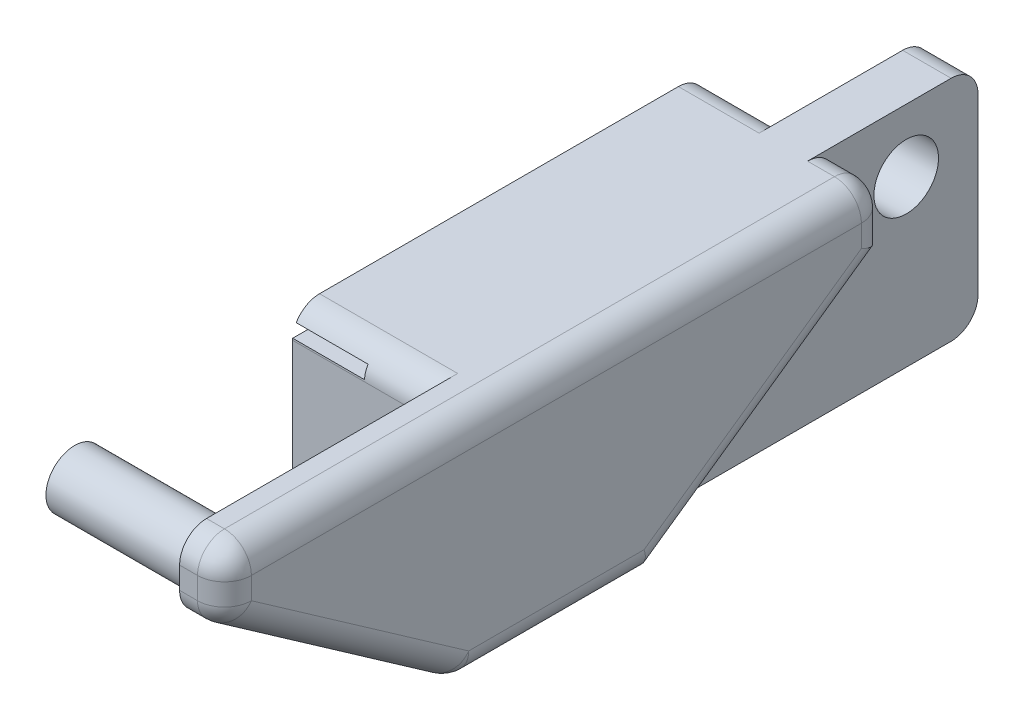
SolidWorks part; units mm, degrees
ref_plane "Front Plane" through (0, 0, 0) normal (0, 0, 1) x (1, 0, 0)
ref_plane "Top Plane" through (0, 0, 0) normal (0, 1, 0) x (1, 0, 0)
ref_plane "Right Plane" through (0, 0, 0) normal (1, 0, 0) x (0, 0, -1)
sketch "Sketch1" plane through (0, 0, 0) normal (0, 1, 0) x (1, 0, 0)
  line L0 (-28.7782, 18.5442) -> (-24.2782, 18.5442)
  line L1 (-24.2782, 18.5442) -> (-24.2782, 26.5442)
  line L2 (-24.2782, 26.5442) -> (-21.5782, 26.5442)
  line L3 (-21.5782, 26.5442) -> (-21.5782, 18.5442)
  line L4 (-21.5782, 18.5442) -> (-18.5782, 18.5442)
  line L5 (-18.5782, 18.5442) -> (-18.5782, -18.4558)
  line L6 (-18.5782, -18.4558) -> (-21.0782, -18.4558)
  line L7 (-21.0782, -18.4558) -> (-21.0782, -4.4558)
  line L10 (-21.0782, -4.4558) -> (-28.7782, -4.4558)
  line L11 (-28.7782, -4.4558) -> (-28.7782, 18.5442)
  dimension "D1" = 10.2
  dimension "D2" = 3
  dimension "D3" = 4.5
  dimension "D4" = 8
  dimension "D5" = 14
  dimension "D6" = 7.7
  dimension "D7" = 45
  dimension "D8" = 8
extrude "Boss-Extrude1" add sketch "Sketch1" along normal blind 12.7
sketch "Sketch2" plane through (-28.7782, 0, 0) normal (-1, 0, 0) x (0, 0, 1)
  line L0 (-26.5442, 12.7) -> (-26.5442, 0)
  line L1 (-26.5442, 0) -> (15.1247, 0)
  line L2 (15.1247, 0) -> (18.4558, 9.2)
  line L3 (18.4558, 9.2) -> (18.4558, 12.7)
  line L4 (18.4558, 12.7) -> (-26.5442, 12.7)
  line L5 (-26.5442, 9.2) -> (18.4558, 9.2) construction
  line L6 (-22.5442, 12.7) -> (-22.5442, 0) construction
  line L7 (-15.2942, 12.7) -> (-15.2942, 0) construction
  line L8 (15.2058, 12.7) -> (15.2058, 0.224) construction
  line L9 (-18.5442, 5.7649) -> (-7.0404, 0)
  line L11 (4.4558, 0) -> (4.4558, 12.7)
  line L13 (-18.5442, 12.7) -> (-18.5442, 5.7649)
  line L14 (-18.5442, 12.7) -> (4.4558, 12.7)
  line L15 (15.1247, 0) -> (18.4558, 0)
  line L16 (-18.5442, 0) -> (4.4558, 0) construction
  line L17 (-18.5442, 12.7) -> (4.4558, 12.7) construction
  line L18 (-7.0404, 0) -> (4.4558, 0)
  line L19 (-18.5442, 5.7649) -> (-18.5442, 0)
  line L20 (-18.5442, 0) -> (-7.0404, 0)
  line L21 (18.4558, 0) -> (18.4558, 9.2)
  line L22 (15.2058, 10.8) -> (-26.5442, 10.8) construction
  line L23 (-26.5442, 11.3) -> (18.4558, 11.3) construction
  line L24 (-18.5442, 12.7) -> (-18.5442, 0) construction
  line L25 (18.4558, 11.95) -> (-26.5442, 11.95)
  line L26 (18.4558, 11.95) -> (18.4558, 11.3)
  line L27 (18.4558, 11.3) -> (-26.5442, 11.3)
  line L28 (-26.5442, 11.95) -> (-26.5442, 11.3)
  line L29 (-18.5442, 12.7) -> (-18.5442, 0) construction
  circle A3 centre (15.2058, 9.2) radius 1.6
  circle A4 centre (-15.2942, 9.2) radius 1.6
  circle A5 centre (-22.5442, 9.2) radius 1.8
  point P35 (-18.5442, 0)
  line M18 (-18.5442, 0) -> (4.4558, 0)
  line M21 (-18.5442, 12.7) -> (-18.5442, 0)
  dimension "D9" = 0.5
  dimension "D1" = 12.7
  dimension "D2" = 3.5
  dimension "D3" = 4
  dimension "D4" = 11.25
  dimension "D5" = 8
  dimension "D6" = 6.5
  dimension "D7" = 14
  dimension "D8" = 45
  dimension "D10" = 0.65
extrude "Cut-Extrude2" cut sketch "Sketch2" along direction (1, 0, 0) on the side against the normal up to surface (4.5 mm away) contours L9 M21 M18 region at (-28.7782, 1.9216, -14.7096) up to face at (-24.2782, 6.35, -22.5442)
extrude "Cut-Extrude3" cut sketch "Sketch2<4>" against normal through all contours L15 L21 L2 region at (-28.7782, 3.0667, 17.3454)
sketch "Sketch2<4>" plane through (-28.7782, 0, 0) normal (-1, 0, 0) x (0, 0, 1) same geometry as "Sketch2"
extrude "Boss-Extrude2" add sketch "Sketch2<5>" along normal blind 9.1 from surface contours A3 region at (-28.7782, 9.2, 15.2058) starting at face at (-21.0782, 6.92, 12.1896)
sketch "Sketch2<5>" plane through (-28.7782, 0, 0) normal (-1, 0, 0) x (0, 0, 1) same geometry as "Sketch2"
extrude "Cut-Extrude4" cut sketch "Sketch2<6>" against normal through all contours A5 region at (-28.7782, 9.2, -22.5442)
sketch "Sketch2<6>" plane through (-28.7782, 0, 0) normal (-1, 0, 0) x (0, 0, 1) same geometry as "Sketch2"
extrude "Boss-Extrude3" add sketch "Sketch2<7>" along normal blind 1.4 contours A4 region at (-28.7782, 9.2, -15.2942)
sketch "Sketch2<7>" plane through (-28.7782, 0, 0) normal (-1, 0, 0) x (0, 0, 1) same geometry as "Sketch2"
extrude "Cut-Extrude5" cut sketch "Sketch2<8>" against normal blind 4 from surface contours L25 L28 L27 L26 starting at face at (-28.7782, 9.2, -16.8942)
sketch "Sketch2<8>" plane through (-28.7782, 0, 0) normal (-1, 0, 0) x (0, 0, 1) same geometry as "Sketch2"
sketch "Sketch3" plane through (-18.5782, 0, 0) normal (1, 0, 0) x (0, 0, -1)
  line L0 (18.5442, 12.7) -> (-18.4558, 12.7)
  line L3 (-18.4558, 0) -> (18.5442, 0)
  line L5 (18.5442, 12.7) -> (18.5442, 9.2)
  line L6 (18.5442, 9.2) -> (5.4052, 0)
  line L7 (5.4052, 0) -> (0.0442, 0)
  line L8 (18.5442, 9.2) -> (18.5442, 0)
  line L9 (18.5442, 0) -> (5.4052, 0)
  line L10 (0.0442, 12.7) -> (0.0442, 0)
  line L11 (-18.4558, 0) -> (-5.3168, 0)
  line L12 (-18.4558, 9.2) -> (-18.4558, 0)
  line L13 (-18.4558, 9.2) -> (-5.3168, 0)
  line L14 (-18.4558, 12.7) -> (-18.4558, 9.2)
  point P9 (18.5442, 12.7)
  point P10 (-18.4558, 12.7)
  point P11 (-18.4558, 0)
  line M7 (-18.4558, 9.2) -> (-15.1247, 0)
  line M8 (-15.1247, 0) -> (18.5442, 0)
  line M9 (18.5442, 0) -> (18.5442, 12.7)
  dimension "D3" = 9.2
  dimension "D4" = 12.7
extrude "Cut-Extrude6" cut sketch "Sketch3" against normal up to surface (3 mm away) contours L6 L3 M9 | L12 L3 M7 | L13 M7 M8 region at (-18.5782, 3.0667, -14.1645) region at (-18.5782, 3.0667, 17.3454) region at (-18.5782, 3.0667, 12.9658) up to face at (-21.5782, 9.2, -20.7442)
sketch "Sketch4" plane through (0, 0, 0) normal (0, -1, 0) x (1, 0, 0)
  line L0 (-22.9282, -26.5442) -> (-22.9282, 4.4558) construction
  line L1 (-21.5782, -26.5442) -> (-24.2782, -26.5442) construction
  line L2 (-28.7782, 4.4558) -> (-21.0782, 4.4558) construction
  line L4 (-22.1782, -26.5442) -> (-23.6782, -26.5442)
  line L5 (-22.1782, -26.5442) -> (-22.1782, 4.4558)
  line L6 (-22.1782, 4.4558) -> (-23.6782, 4.4558)
  line L7 (-23.6782, -26.5442) -> (-23.6782, 4.4558)
  dimension "D1" = 0.75
  dimension "D2" = 0.75
extrude "Cut-Extrude7" cut sketch "Sketch4" against normal blind 3
sketch "Sketch6" plane through (0, 0, 0) normal (0, -1, 0) x (-1, 0, 0)
  line L1 (23.6782, -4.4558) -> (21.5782, -4.4558)
  line L2 (23.6782, -4.4558) -> (23.6782, 2.4052)
  line L3 (23.6782, 2.4052) -> (21.5782, 2.4052)
  line L4 (21.5782, -4.4558) -> (21.5782, 2.4052)
extrude "Boss-Extrude4" add sketch "Sketch6" against normal blind 1
sketch "Sketch8" plane through (-28.7782, 0, 0) normal (-1, 0, 0) x (0, 0, 1)
  line L0 (-1.5442, 12.7) -> (-18.5442, 12.7)
  line L1 (-18.5442, 0) -> (-1.5442, 0)
  line L7 (-1.5442, 12.7) -> (-1.5442, 0)
  line L8 (-18.5442, 0) -> (-5.4052, 0)
  line L9 (-18.5442, 9.2) -> (-18.5442, 0)
  line L10 (-18.5442, 9.2) -> (-5.4052, 0)
  line L11 (-18.5442, 12.7) -> (-18.5442, 9.2)
  point P2 (-18.5442, 12.7)
  line M7 (-18.5442, 5.7649) -> (-7.0404, 0)
  line M9 (-7.0404, 0) -> (4.4558, 0)
  line M19 (-18.5442, 11.3) -> (-18.5442, 5.7649)
  dimension "D1" = 13.139
  dimension "D2" = 12.7
  dimension "D3" = 9.2
  dimension "D4" = 17
extrude "Cut-Extrude8" cut sketch "Sketch8" against normal up to surface (4.5 mm away) contours L9 L1 M7 | L10 M19 M7 M9 region at (-28.7782, 4.4585, -13.502) region at (-28.7782, 1.9216, -14.7096) up to face at (-24.2782, 9.2, -24.3442)
fillet "Fillet1" radius 1.5 18 edges at (-24.9282, 0, 4.4558) (-24.9282, 12.7, 4.4558) (-21.8782, 0, -26.5442) (-23.9782, 0, -26.5442) (-22.9282, 12.7, -26.5442) (-18.5782, 10.95, 18.4558) (-19.8282, 9.2, 18.4558) (-19.8282, 12.7, 18.4558) (-19.8282, 0, 5.3168) (-18.5782, 4.6, 11.8863) (-18.5782, 0, -0.0442) (-18.5782, 4.6, -11.9747) (-18.5782, 10.95, -18.5442) (-26.5282, 12.7, -18.5442) (-20.0782, 12.7, -18.5442) (-18.5782, 12.7, -0.0442) (-26.5282, 0, -5.4052) (-26.5282, 9.2, -18.5442)
fillet "Fillet2" radius 0.25 14 edges at (-23.6782, 0, -13.7247) (-22.1782, 0, -13.7247) (-23.6782, 0.4393, -26.1049) (-22.1782, 0.4393, -26.1049) (-23.6782, 1.2463, 4.4342) (-22.1782, 1.2463, 4.4342) (-23.6782, 2.25, -26.5442) (-22.1782, 2.25, -26.5442) (-23.6782, 2.25, 4.4558) (-22.1782, 2.25, 4.4558) (-22.9282, 3, -26.5442) (-23.6782, 3, -11.0442) (-22.9282, 3, 4.4558) (-22.1782, 3, -11.0442)
